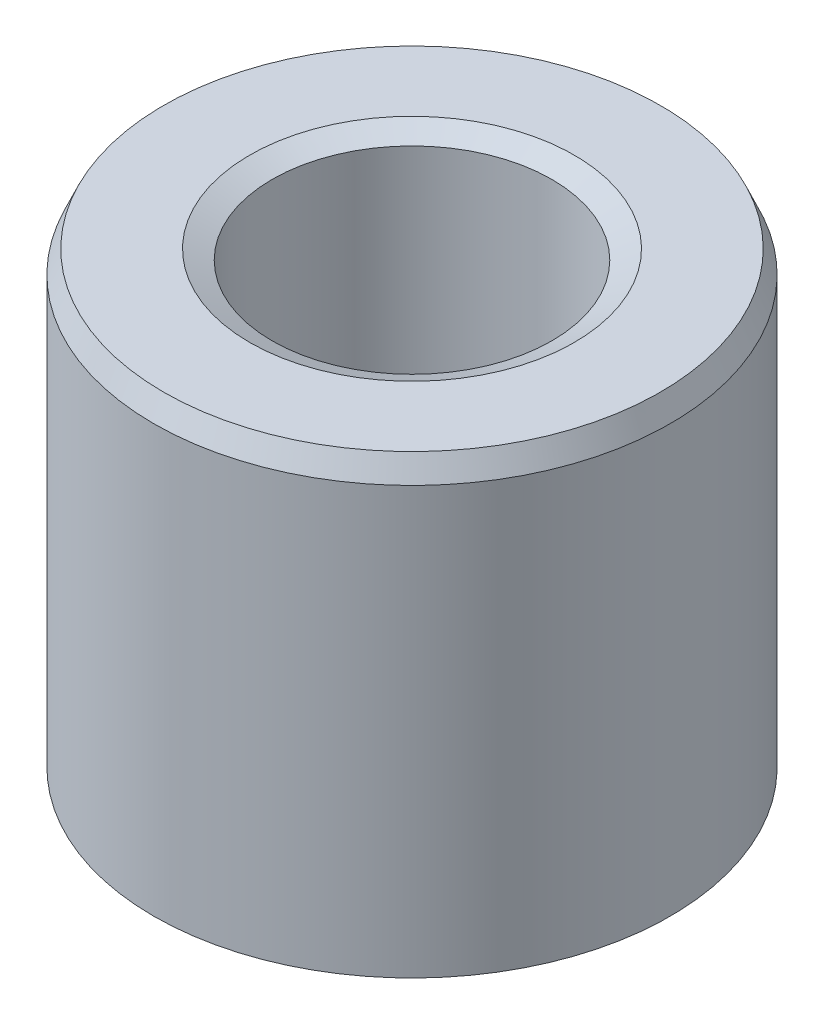
SolidWorks part; units mm, degrees
ref_plane "Front Plane" through (0, 0, 0) normal (0, 0, 1) x (1, 0, 0)
ref_plane "Top Plane" through (0, 0, 0) normal (0, 1, 0) x (1, 0, 0)
ref_plane "Right Plane" through (0, 0, 0) normal (1, 0, 0) x (0, 0, -1)
sketch "Sketch1" plane through (0, 0, 0) normal (0, 1, 0) x (1, 0, 0)
  circle A0 centre (0, 0) radius 30
  dimension "SLEEVE_OD" = 60
extrude "Boss-Extrude1" add sketch "Sketch1" along normal blind 53.3105
sketch "Sketch2" plane through (0, 0, 0) normal (0, 1, 0) x (1, 0, 0)
  circle A0 centre (0, 0) radius 16.2526
  dimension "BORE_D" = 32.5052
extrude "Cut-Extrude1" cut sketch "Sketch2" along normal through all
chamfer "Chamfer1" distance 2.605 angle 23.644 4 edges at (0, 53.3105, 16.2526) (0, 0, 16.2526) (0, 0, 30) (0, 53.3105, 30) first distance on face at (0, 53.3105, 16.2526) first distance on face at (0, 0, 16.2526) first distance on face at (0, 53.3105, 30)
